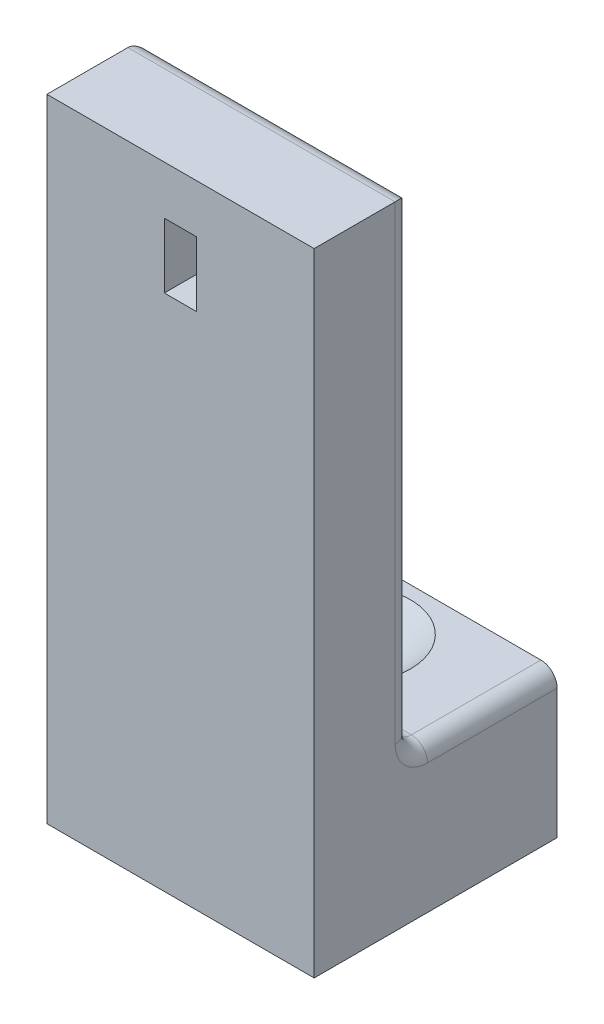
SolidWorks part; units mm, degrees
ref_plane "Front Plane" through (0, 0, 0) normal (0, 0, 1) x (1, 0, 0)
ref_plane "Top Plane" through (0, 0, 0) normal (0, 1, 0) x (1, 0, 0)
ref_plane "Right Plane" through (0, 0, 0) normal (1, 0, 0) x (0, 0, -1)
sketch "Sketch1" plane through (0, 0, 0) normal (0, 1, 0) x (1, 0, 0)
  line L1 (-8.25, 7.5) -> (8.25, 7.5)
  line L2 (-8.25, 7.5) -> (-8.25, -7.5)
  line L3 (-8.25, -7.5) -> (8.25, -7.5)
  line L4 (8.25, 7.5) -> (8.25, -7.5)
  line L5 (-8.25, 7.5) -> (8.25, -7.5) construction
  line L6 (-8.25, -7.5) -> (8.25, 7.5) construction
  circle A0 centre (0, 3) radius 2.2
  point P0 (0, 0)
  dimension "D3" = 4.4
  dimension "D1" = 16.5
  dimension "D2" = 15
  dimension "D4" = 4.5
extrude "Boss-Extrude1" add sketch "Sketch1" along normal blind 9
chamfer "Chamfer1" distance 1.5 angle 45 1 edges at (0, 9, -0.8)
sketch "Sketch2" plane through (0, 9, 0) normal (0, 1, 0) x (1, 0, 0)
  line L0 (-8.25, 7.5) -> (-8.25, -7.5) construction
  line L1 (-8.25, -1.5) -> (8.25, -1.5)
  line L2 (-8.25, -1.5) -> (-8.25, -7.5)
  line L3 (-8.25, -7.5) -> (8.25, -7.5)
  line L4 (8.25, -1.5) -> (8.25, -7.5)
  line L5 (8.25, -7.5) -> (8.25, 7.5) construction
  dimension "D1" = 6
extrude "Boss-Extrude2" add sketch "Sketch2" along normal blind 30
sketch "Sketch4" plane through (0, 0, 1.5) normal (0, 0, -1) x (-1, 0, 0)
  line L0 (0, 32) -> (0, 36) construction
  line L1 (-1, 36) -> (1, 36)
  line L2 (-1, 36) -> (-1, 32)
  line L3 (-1, 32) -> (1, 32)
  line L4 (1, 36) -> (1, 32)
  line L5 (-8.25, 39) -> (8.25, 39) construction
  line L6 (-2, 37) -> (2, 37)
  line L7 (2, 37) -> (2, 31)
  line L8 (-2, 31) -> (2, 31)
  line L9 (-2, 37) -> (-2, 31)
  dimension "D1" = 2
  dimension "D2" = 4
  dimension "D3" = 3
  dimension "D4" = 1
extrude "Cut-Extrude2" cut sketch "Sketch4" against normal through all both contours L0 L3 L4 L1 | L3 L0 L1 L2 region at (0.5, 34, 1.5) region at (-0.5, 34, 1.5)
extrude "Cut-Extrude3" cut sketch "Sketch4<3>" against normal blind 1 contours L6 L9 L8 L7 L1 L4 L3 L2 region at (0, 36.9279, 1.5)
sketch "Sketch4<3>" plane through (0, 0, 1.5) normal (0, 0, -1) x (-1, 0, 0) same geometry as "Sketch4"
fillet "Fillet1" radius 1 6 edges at (8.25, 24, 1.5) (-8.25, 9, -3) (0, 39, 1.5) (8.25, 9, -3) (-8.25, 24, 1.5) (0, 9, 1.5)
sketch "Sketch7" plane through (0, 0, 2.5) normal (0, 0, -1) x (-1, 0, 0)
  line L0 (-2, 37) -> (-2, 31) construction
  line L1 (-2, 32) -> (2, 32)
  line L2 (-2, 32) -> (-2, 31)
  line L3 (-2, 31) -> (2, 31)
  line L4 (2, 32) -> (2, 31)
  line L5 (-1, 32) -> (1, 32) construction
extrude "Boss-Extrude4" add sketch "Sketch7" along normal blind 1
